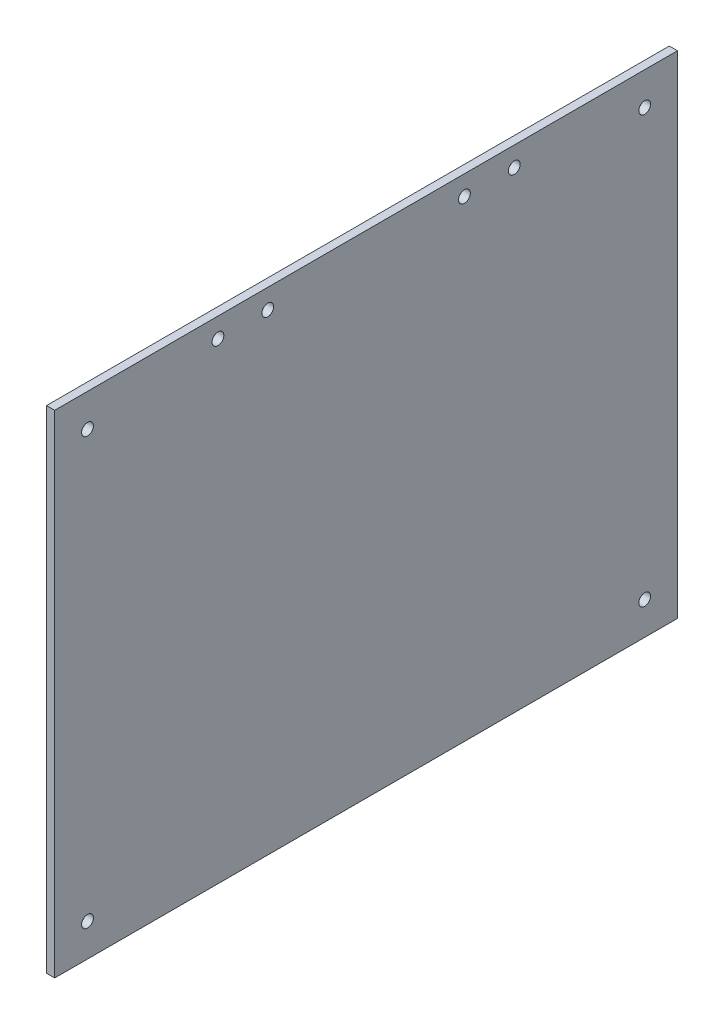
SolidWorks part; units mm, degrees
ref_plane "Front Plane" through (0, 0, 0) normal (0, 0, 1) x (1, 0, 0)
ref_plane "Top Plane" through (0, 0, 0) normal (0, 1, 0) x (1, 0, 0)
ref_plane "Right Plane" through (0, 0, 0) normal (1, 0, 0) x (0, 0, -1)
sketch "Sketch1" plane through (0, 0, 0) normal (1, 0, 0) x (0, 0, -1)
  line L1 (0, 0) -> (241.3, 0)
  line L2 (0, 0) -> (0, 190.5)
  line L3 (0, 190.5) -> (241.3, 190.5)
  line L4 (241.3, 0) -> (241.3, 190.5)
  dimension "D1" = 241.3
  dimension "D2" = 190.5
extrude "Boss-Extrude1" add sketch "Sketch1" along normal blind 3.175
sketch "Sketch2" plane through (3.175, 0, 0) normal (1, 0, 0) x (0, 0, -1)
  line L2 (-1000, 95.25) -> (49000, 95.25) construction
  line L3 (0, 190.5) -> (0, 0) construction
  line L4 (120.65, -809.5) -> (120.65, 49190.5) construction
  line L5 (241.3, 190.5) -> (0, 190.5) construction
  line L6 (1228.6, 95.25) -> (-48771.4, 95.25) construction
  line L7 (241.3, 0) -> (241.3, 190.5) construction
  line L8 (0, 0) -> (241.3, 0) construction
  circle A8 centre (228.6, 12.7) radius 2.286
  circle A9 centre (228.6, 177.8) radius 2.286
  circle A10 centre (12.7, 12.7) radius 2.286
  circle A11 centre (12.7, 177.8) radius 2.286
  point P15 (0, 95.25)
  point P20 (120.65, 190.5)
  dimension "D1" = 4.572
  dimension "D3" = 12.7
  dimension "D2" = 12.7
extrude "Cut-Extrude1" cut sketch "Sketch2" against normal through all
sketch "Sketch3" plane through (3.175, 0, 0) normal (1, 0, 0) x (0, 0, -1)
  line L0 (241.3, 190.5) -> (0, 190.5) construction
  circle A0 centre (63.246, 182.88) radius 2.286
  circle A1 centre (82.55, 182.88) radius 2.286
  circle A2 centre (158.75, 182.88) radius 2.286
  circle A3 centre (178.054, 182.88) radius 2.286
  point P11 (120.65, 190.5)
  dimension "D1" = 4.572
  dimension "D2" = 19.304
  dimension "D4" = 7.62
  dimension "D3" = 19.304
  dimension "D5" = 38.1
  dimension "D6" = 38.1
extrude "Cut-Extrude2" cut sketch "Sketch3" against normal through all
